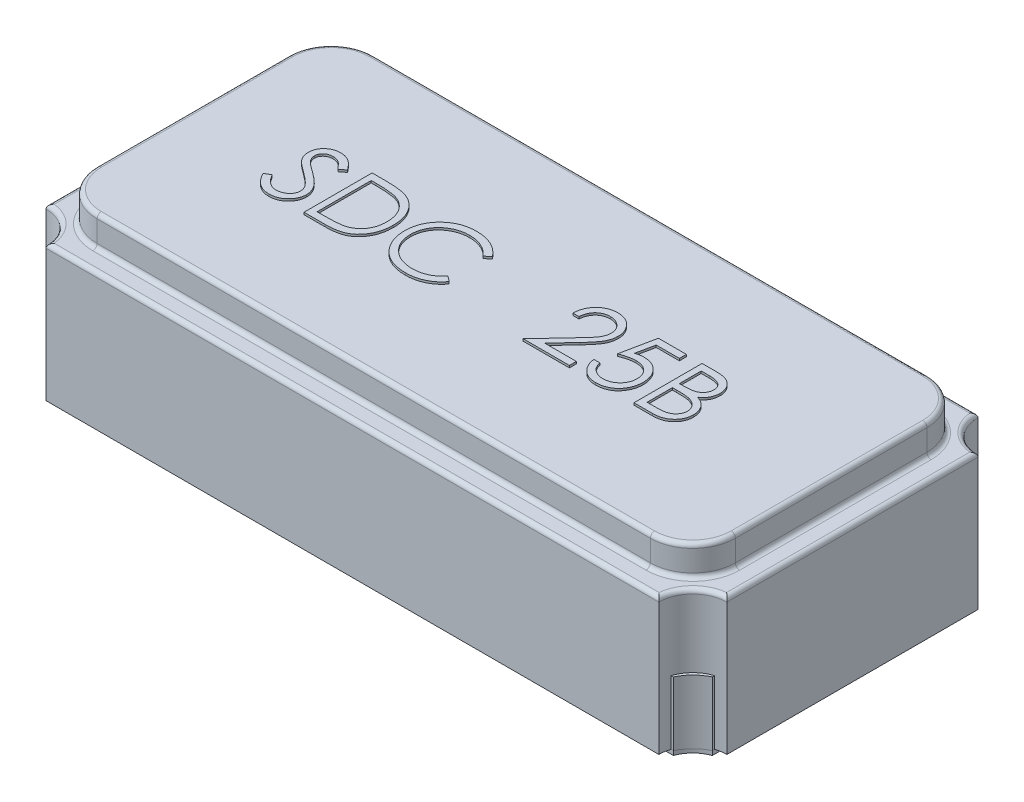
SolidWorks part; units mm, degrees
ref_plane "Спереди" through (0, 0, 0) normal (0, 0, 1) x (1, 0, 0)
ref_plane "Сверху" through (0, 0, 0) normal (0, 1, 0) x (1, 0, 0)
ref_plane "Справа" through (0, 0, 0) normal (1, 0, 0) x (0, 0, -1)
sketch "Эскиз2" plane through (0, 0, 0) normal (0, 1, 0) x (1, 0, 0)
  line L0 (0, -0.7737) -> (0, 0.9108) construction
  line L1 (1.7122, 0) -> (-1.6552, 0) construction
  line L2 (1.6, -0.75) -> (-1.6, -0.75) construction
  line L3 (1.6, -0.75) -> (1.6, 0.75) construction
  line L4 (1.6, 0.75) -> (-1.6, 0.75) construction
  line L5 (-1.6, -0.75) -> (-1.6, 0.75) construction
  line L6 (1.6, -0.75) -> (-1.6, 0.75) construction
  line L7 (1.6, 0.75) -> (-1.6, -0.75) construction
  line L8 (1.55, -0.7) -> (-1.55, -0.7) construction
  line L9 (1.55, -0.7) -> (1.55, 0.7) construction
  line L10 (1.55, 0.7) -> (-1.55, 0.7) construction
  line L11 (-1.55, -0.7) -> (-1.55, 0.7) construction
  line L12 (1.55, -0.7) -> (-1.55, 0.7) construction
  line L13 (1.55, 0.7) -> (-1.55, -0.7) construction
  line L14 (0.825, -0.75) -> (-0.825, -0.75) construction
  line L15 (0.825, -0.75) -> (0.825, 0.75) construction
  line L16 (0.825, 0.75) -> (-0.825, 0.75) construction
  line L17 (-0.825, -0.75) -> (-0.825, 0.75) construction
  line L18 (0.825, -0.75) -> (-0.825, 0.75) construction
  line L19 (0.825, 0.75) -> (-0.825, -0.75) construction
  line L20 (-1.4586, 0.7) -> (-0.825, 0.7)
  line L21 (-0.825, 0.7) -> (-0.825, 0.1984)
  line L22 (-0.825, -0.7) -> (-1.4586, -0.7)
  line L23 (-1.55, 0.6086) -> (-1.55, -0.6086)
  line L24 (1.55, 0.6086) -> (1.55, -0.6086)
  line L25 (0.825, -0.7) -> (1.4586, -0.7)
  line L26 (0.825, 0.7) -> (0.825, -0.7)
  line L27 (1.4586, 0.7) -> (0.825, 0.7)
  line L28 (-0.825, -0.1984) -> (-0.825, -0.7)
  circle A0 centre (-1.6, -0.75) radius 0.15 construction
  circle A1 centre (1.6, -0.75) radius 0.15 construction
  circle A2 centre (-1.6, 0.75) radius 0.15 construction
  circle A3 centre (1.6, 0.75) radius 0.15 construction
  arc A4 (-0.825, 0.1984) -> (-0.825, -0.1984) centre (-0.825, 0) cw
  arc A5 (-1.55, 0.6086) -> (-1.4586, 0.7) centre (-1.6, 0.75) ccw
  arc A6 (-1.55, -0.6086) -> (-1.4586, -0.7) centre (-1.6, -0.75) cw
  arc A7 (1.55, -0.6086) -> (1.4586, -0.7) centre (1.6, -0.75) ccw
  arc A8 (1.55, 0.6086) -> (1.4586, 0.7) centre (1.6, 0.75) cw
  point P2 (0, 0)
  point P9 (0, 0)
  point P20 (0, 0)
  dimension "D5" = 0.3
  dimension "D1" = 3.2
  dimension "D2" = 1.5
  dimension "D3" = 2
  dimension "D4" = 2
  dimension "D8" = 1.65
  dimension "D6" = 3.1
  dimension "D7" = 2
extrude "Бобышка-Вытянуть2" add sketch "Эскиз2" along normal blind 0.02
ref_plane "Плоскость1" through (0, 0.02, 0) normal (0, 1, 0) x (-1, 0, 0)
sketch "Эскиз5" plane through (0, 0.02, 0) normal (0, 1, 0) x (-1, 0, 0)
  line L0 (0, -0.8137) -> (0, 0.8285) construction
  line L1 (0.9756, 0) -> (-1.114, 0) construction
  line L8 (1.4586, 0.7) -> (0.825, 0.7) construction
  line L9 (1.55, -0.6086) -> (1.55, 0.6086) construction
  line L10 (1.4586, 0.7) -> (1.4365, 0.7)
  line L11 (1.55, 0.6086) -> (1.55, 0.5865)
  line L12 (1.4586, -0.7) -> (1.4365, -0.7)
  line L13 (1.55, -0.6086) -> (1.55, -0.5865)
  line L14 (-1.4586, -0.7) -> (-1.4365, -0.7)
  line L15 (-1.55, -0.6086) -> (-1.55, -0.5865)
  line L16 (-1.55, 0.6086) -> (-1.55, 0.5865)
  line L17 (-1.4586, 0.7) -> (-1.4365, 0.7)
  arc A0 (1.55, 0.6086) -> (1.4586, 0.7) centre (1.6381, 0.7881) cw
  arc A1 (1.4365, 0.7) -> (1.55, 0.5865) centre (1.6381, 0.7881) ccw
  arc A2 (1.4365, -0.7) -> (1.55, -0.5865) centre (1.6381, -0.7881) cw
  arc A3 (1.55, -0.6086) -> (1.4586, -0.7) centre (1.6381, -0.7881) ccw
  arc A4 (-1.55, -0.6086) -> (-1.4586, -0.7) centre (-1.6381, -0.7881) cw
  arc A5 (-1.4365, -0.7) -> (-1.55, -0.5865) centre (-1.6381, -0.7881) ccw
  arc A6 (-1.55, 0.6086) -> (-1.4586, 0.7) centre (-1.6381, 0.7881) ccw
  arc A7 (-1.4365, 0.7) -> (-1.55, 0.5865) centre (-1.6381, 0.7881) cw
  dimension "D1" = 0.2
  dimension "D2" = 0.22
extrude "Бобышка-Вытянуть4" add sketch "Эскиз5" along normal blind 0.3
sketch "Эскиз6" plane through (0, 0.02, 0) normal (0, 1, 0) x (-1, 0, 0)
  line L0 (1.0415, 0) -> (-1.2862, 0) construction
  line L1 (-1.6, 0.75) -> (1.6, 0.75) construction
  line L2 (-1.6, 0.75) -> (-1.6, -0.75) construction
  line L3 (-1.6, -0.75) -> (1.6, -0.75) construction
  line L4 (1.6, 0.75) -> (1.6, -0.75) construction
  line L5 (-1.6, 0.75) -> (1.6, -0.75) construction
  line L6 (-1.6, -0.75) -> (1.6, 0.75) construction
  line L8 (0, -0.6677) -> (0, 1.0278) construction
  line L9 (1.44, -0.75) -> (-1.44, -0.75)
  line L10 (-1.6, -0.59) -> (-1.6, 0.59)
  line L13 (-1.44, 0.75) -> (1.44, 0.75)
  line L15 (1.6, 0.59) -> (1.6, -0.59)
  arc A0 (1.44, 0.75) -> (1.6, 0.59) centre (1.6, 0.75) ccw
  arc A2 (1.44, -0.75) -> (1.6, -0.59) centre (1.6, -0.75) cw
  arc A3 (-1.44, 0.75) -> (-1.6, 0.59) centre (-1.6, 0.75) cw
  arc A4 (-1.44, -0.75) -> (-1.6, -0.59) centre (-1.6, -0.75) ccw
  point P0 (0, 0)
  dimension "D3" = 0.16
  dimension "D1" = 3.2
  dimension "D2" = 1.5
extrude "Бобышка-Вытянуть8" add sketch "Эскиз6" along normal blind 0.64
ref_plane "Плоскость3" through (0, 0.66, 0) normal (0, 1, 0) x (-1, 0, 0)
sketch "Эскиз7" plane through (0, 0.66, 0) normal (0, 1, 0) x (-1, 0, 0)
  line L1 (-1.5, 0.65) -> (1.5, 0.65)
  line L2 (-1.5, 0.65) -> (-1.5, -0.65)
  line L3 (-1.5, -0.65) -> (1.5, -0.65)
  line L4 (1.5, 0.65) -> (1.5, -0.65)
  line L5 (-1.5, 0.65) -> (1.5, -0.65) construction
  line L6 (-1.5, -0.65) -> (1.5, 0.65) construction
  point P0 (0, 0)
  dimension "D1" = 3
  dimension "D2" = 1.3
extrude "Бобышка-Вытянуть9" add sketch "Эскиз7" along normal blind 0.14
sketch "Эскиз8" plane through (0, 0.8, 0) normal (0, 1, 0) x (-1, 0, 0)
  line L0 (1.0732, 0.1668) -> (-1.1486, 0.1668) construction
  text T0 "SDC   25B" font "Century Gothic" height 0.32
fillet "Скругление3" radius 0.2 4 edges at (1.5, 0.73, -0.65) (1.5, 0.73, 0.65) (-1.5, 0.73, -0.65) (-1.5, 0.73, 0.65)
fillet "Скругление4" radius 0.02 8 edges at (1.4414, 0.8, 0.5914) (0, 0.8, 0.65) (-1.4414, 0.8, 0.5914) (-1.5, 0.8, 0) (-1.4414, 0.8, -0.5914) (0, 0.8, -0.65) (1.4414, 0.8, -0.5914) (1.5, 0.8, 0)
fillet "Скругление5" radius 0.02 8 edges at (-1.4414, 0.66, 0.5914) (-1.5, 0.66, 0) (-1.4414, 0.66, -0.5914) (0, 0.66, -0.65) (1.4414, 0.66, -0.5914) (1.5, 0.66, 0) (1.4414, 0.66, 0.5914) (0, 0.66, 0.65)
fillet "Скругление6" radius 0.02 8 edges at (-1.6, 0.66, 0) (-1.4869, 0.66, -0.6369) (0, 0.66, -0.75) (1.4869, 0.66, -0.6369) (1.6, 0.66, 0) (1.4869, 0.66, 0.6369) (0, 0.66, 0.75) (-1.4869, 0.66, 0.6369)
extrude "Бобышка-Вытянуть10" add sketch "Эскиз8" along normal blind 0.01
